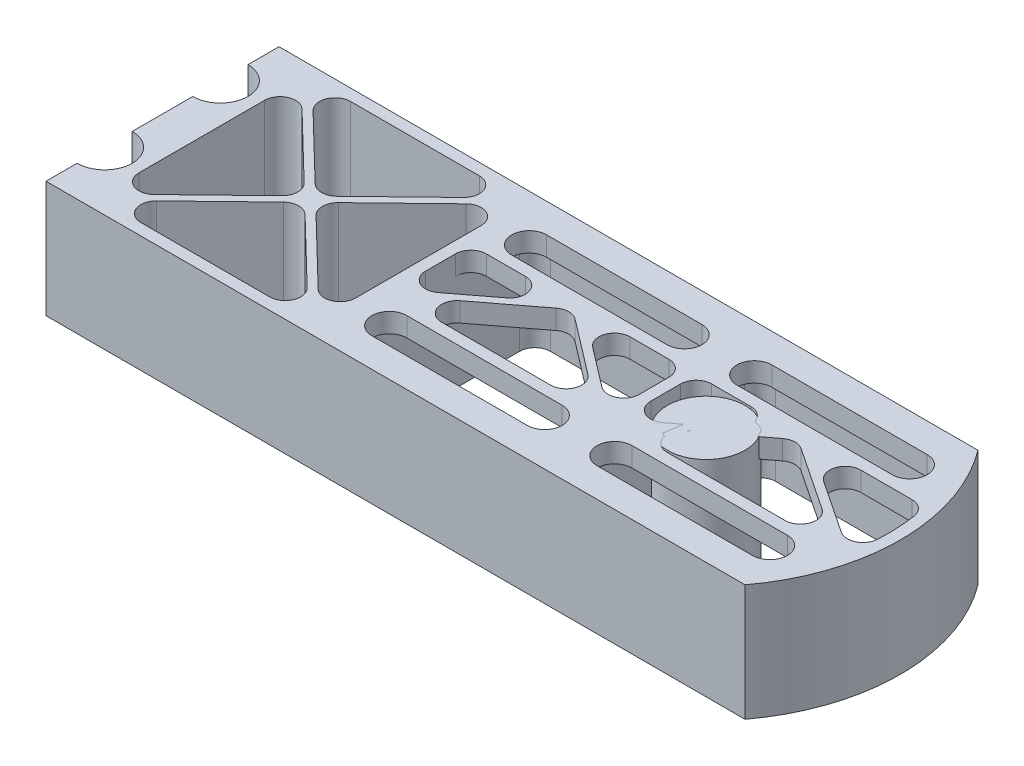
SolidWorks part; units mm, degrees
material "3.1355 (EN-AW 2024)"
ref_plane "Front" through (0, 0, 0) normal (0, 0, 1) x (1, 0, 0)
ref_plane "Top" through (0, 0, 0) normal (0, 1, 0) x (1, 0, 0)
ref_plane "Right" through (0, 0, 0) normal (1, 0, 0) x (0, 0, -1)
sketch "Эскиз1" plane through (0, 0, 0) normal (0, 1, 0) x (1, 0, 0)
  line L0 (0, 0) -> (0, 60) construction
  line L1 (0, 60) -> (180, 60)
  line L2 (190, 60) -> (190, 0) construction
  line L3 (190, 0) -> (180, 0) construction
  line L4 (0, 30) -> (140, 30) construction
  line L5 (0, 60) -> (0, 52)
  line L6 (0, 37.8) -> (0, 22.2)
  line L7 (0, 8) -> (0, 0)
  line L8 (140, 30) -> (190, 30) construction
  line L9 (180, 60) -> (190, 60) construction
  line L10 (180, 0) -> (0, 0)
  circle A0 centre (0, 44.9) radius 7.1 construction
  circle A1 centre (0, 15.1) radius 7.1 construction
  arc A2 (0, 52) -> (0, 37.8) centre (0, 44.9) cw
  arc A3 (0, 8) -> (0, 22.2) centre (0, 15.1) ccw
  arc A4 (180, 0) -> (180, 60) centre (140, 30) ccw
  point P11 (0, 52)
  point P12 (0, 37.8)
  point P20 (180.1659, -0.1217)
  dimension "D2" = 14.2
  dimension "D4" = 29.8
  dimension "D8" = 50
  dimension "D1" = 60
  dimension "D3" = 15.1
  dimension "D5" = 140
  dimension "D6" = 50
  dimension "D7" = 190
extrude "Бобышка-Вытянуть1" add sketch "Эскиз1" along normal blind 30
sketch "Эскиз2" plane through (0, 30, 0) normal (0, 1, 0) x (1, 0, 0)
  line L5 (3, 3) -> (178.4708, 3)
  line L6 (3, 3) -> (178.4708, 3)
  line L12 (3, 5.4558) -> (3, 3)
  line L15 (178.4708, 57) -> (3, 57)
  line L16 (3, 57) -> (3, 54.5442)
  line L17 (3, 35.2558) -> (3, 24.7442)
  line L18 (3, 5.4558) -> (3, 3)
  line L21 (178.4708, 57) -> (3, 57)
  line L22 (3, 57) -> (3, 54.5442)
  line L23 (3, 35.2558) -> (3, 24.7442)
  arc A3 (178.4708, 3) -> (178.4708, 57) centre (140, 30) ccw
  arc A4 (3, 35.2558) -> (3, 54.5442) centre (0, 44.9) ccw
  arc A5 (3, 5.4558) -> (3, 24.7442) centre (0, 15.1) ccw
  arc A6 (3, 35.2558) -> (3, 54.5442) centre (0, 44.9) ccw
  arc A7 (3, 5.4558) -> (3, 24.7442) centre (0, 15.1) ccw
  arc A8 (178.4708, 3) -> (178.4708, 57) centre (140, 30) ccw
  dimension "D1" = 3
extrude "Вырез-Вытянуть1" cut sketch "Эскиз2" against normal through all
sketch "Temp" plane through (0, 30, 0) normal (0, 1, 0) x (1, 0, 0)
  circle A0 centre (140, 30) radius 10
  dimension "D1" = 20
extrude "Бобышка-Вытянуть2" add sketch "Temp" against normal up to surface (30 mm away) separate body up to face at (49.7088, 0, -30)
sketch "Эскиз3" plane through (0, 30, 0) normal (0, 1, 0) x (1, 0, 0)
  line L0 (178.4708, 57) -> (3, 57) construction
  line L1 (174.4166, 48) -> (134.4166, 48) construction
  line L2 (174.4166, 43.5) -> (134.4166, 43.5)
  line L3 (174.4166, 52.5) -> (134.4166, 52.5)
  line L4 (174.4166, 48) -> (183.4166, 48) construction
  line L5 (125.4166, 57) -> (125.4166, 30) construction
  line L6 (0, 30) -> (140, 30) construction
  line L7 (76.4166, 48) -> (116.4166, 48) construction
  line L8 (76.4166, 43.5) -> (116.4166, 43.5)
  line L9 (76.4166, 52.5) -> (116.4166, 52.5)
  line L10 (187, 30) -> (125.4166, 30) construction
  line L11 (76.4166, 12) -> (116.4166, 12) construction
  line L12 (76.4166, 16.5) -> (116.4166, 16.5)
  line L13 (76.4166, 7.5) -> (116.4166, 7.5)
  line L14 (174.4166, 12) -> (134.4166, 12) construction
  line L15 (174.4166, 16.5) -> (134.4166, 16.5)
  line L16 (174.4166, 7.5) -> (134.4166, 7.5)
  line L17 (68.9166, 57) -> (68.9166, 40.5)
  line L18 (68.9166, 40.5) -> (185.8121, 40.5)
  line L19 (178.4708, 57) -> (68.9166, 57)
  line L20 (76.4166, 12) -> (116.4166, 12) construction
  line L21 (76.4166, 16.5) -> (116.4166, 16.5)
  line L22 (76.4166, 7.5) -> (116.4166, 7.5)
  line L23 (174.4166, 12) -> (134.4166, 12) construction
  line L24 (174.4166, 16.5) -> (134.4166, 16.5)
  line L25 (174.4166, 7.5) -> (134.4166, 7.5)
  line L26 (68.9166, 19.5) -> (185.8121, 19.5)
  line L27 (178.4708, 3) -> (68.9166, 3)
  line L28 (68.9166, 3) -> (68.9166, 19.5)
  arc A0 (174.4166, 43.5) -> (174.4166, 52.5) centre (174.4166, 48) ccw
  arc A1 (134.4166, 52.5) -> (134.4166, 43.5) centre (134.4166, 48) ccw
  arc A2 (178.4708, 3) -> (178.4708, 57) centre (140, 30) ccw construction
  arc A3 (76.4166, 43.5) -> (76.4166, 52.5) centre (76.4166, 48) cw
  arc A4 (116.4166, 52.5) -> (116.4166, 43.5) centre (116.4166, 48) cw
  arc A5 (76.4166, 16.5) -> (76.4166, 7.5) centre (76.4166, 12) ccw
  arc A6 (116.4166, 7.5) -> (116.4166, 16.5) centre (116.4166, 12) ccw
  arc A7 (174.4166, 16.5) -> (174.4166, 7.5) centre (174.4166, 12) cw
  arc A8 (134.4166, 7.5) -> (134.4166, 16.5) centre (134.4166, 12) cw
  arc A9 (185.8121, 40.5) -> (178.4708, 57) centre (140, 30) ccw
  arc A10 (76.4166, 16.5) -> (76.4166, 7.5) centre (76.4166, 12) ccw
  arc A11 (116.4166, 7.5) -> (116.4166, 16.5) centre (116.4166, 12) ccw
  arc A12 (174.4166, 16.5) -> (174.4166, 7.5) centre (174.4166, 12) cw
  arc A13 (134.4166, 7.5) -> (134.4166, 16.5) centre (134.4166, 12) cw
  arc A14 (185.8121, 19.5) -> (178.4708, 3) centre (140, 30) cw
  point P1 (154.4166, 48)
  point P20 (96.4166, 48)
  point P28 (96.4166, 12)
  point P35 (154.4166, 12)
  arc M3 (178.4708, 57) -> (178.4708, 3) centre (140, 30) cw
  line M4 (178.4708, 3) -> (3, 3)
  line M10 (3, 57) -> (178.4708, 57)
  dimension "D1" = 4.5
  dimension "D6" = 3
  dimension "D2" = 40
  dimension "D3" = 9
  dimension "D4" = 9
  dimension "D5" = 9
  dimension "D7" = 7.5
extrude "Бобышка-Вытянуть3" add sketch "Эскиз3" against normal blind 5 contours L17 L18 A1 L3 A0 L2 L9 A4 L8 A3 M3 M10 | L28 L26 A6 L13 A5 L12 L16 A8 L15 A7 M4 M3 region at (126.2402, 30, -49.206) region at (126.2402, 30, -10.794)
sketch "Эскиз4" plane through (0, 30, 0) normal (0, 1, 0) x (1, 0, 0)
  line L0 (3, 57) -> (3, 54.5442) construction
  line L1 (3, 35.2558) -> (3, 24.7442) construction
  line L2 (3, 5.4558) -> (3, 3) construction
  line L3 (3, 3) -> (68.9166, 3) construction
  line L4 (68.9166, 57) -> (3, 57) construction
  line L5 (3, 57) -> (3, 54.5442)
  line L6 (3, 35.2558) -> (3, 24.7442)
  line L7 (3, 5.4558) -> (3, 3)
  line L8 (3, 3) -> (10.1, 3)
  line L9 (10.1, 57) -> (3, 57)
  line L10 (10.1, 57) -> (10.1, 3)
  arc A0 (3, 35.2558) -> (3, 54.5442) centre (0, 44.9) ccw construction
  arc A1 (3, 5.4558) -> (3, 24.7442) centre (0, 15.1) ccw construction
  arc A2 (3, 35.2558) -> (3, 54.5442) centre (0, 44.9) ccw
  arc A3 (3, 5.4558) -> (3, 24.7442) centre (0, 15.1) ccw
  line M4 (68.9166, 3) -> (3, 3)
  line M5 (3, 3) -> (3, 5.4558)
  arc M6 (3, 5.4558) -> (3, 24.7442) centre (0, 15.1) ccw
  line M7 (3, 24.7442) -> (3, 35.2558)
  arc M8 (3, 35.2558) -> (3, 54.5442) centre (0, 44.9) ccw
  line M9 (3, 54.5442) -> (3, 57)
  line M10 (3, 57) -> (68.9166, 57)
extrude "Бобышка-Вытянуть4" add sketch "Эскиз4" against normal through all contours L10 M10 M9 M8 | L10 M8 M7 M6 | L10 M6 M5 M4 region at (7.3993, 30, -54.0144) region at (7.3993, 30, -5.9856) region at (7.0952, 30, -30)
sketch "Эскиз6" plane through (0, 30, 0) normal (0, 1, 0) x (1, 0, 0)
  line L0 (65.9166, 57) -> (65.9166, 3)
  line L1 (68.9166, 57) -> (10.1, 57) construction
  line L2 (10.1, 3) -> (68.9166, 3) construction
  line L3 (68.9166, 57) -> (68.9166, 40.5) construction
  line L4 (65.9166, 3) -> (68.9166, 3)
  line L5 (68.9166, 3) -> (68.9166, 57)
  line L6 (68.9166, 57) -> (65.9166, 57)
  dimension "D1" = 3
extrude "Бобышка-Вытянуть5" add sketch "Эскиз6" against normal through all
sketch "Эскиз7" plane through (0, 30, 0) normal (0, 1, 0) x (1, 0, 0)
  line L0 (10.1, 3) -> (65.9166, 57) construction
  line L1 (10.1, 57) -> (65.9166, 3) construction
  line L2 (10.1, 55.6086) -> (36.5701, 30)
  line L3 (11.5382, 3) -> (38.0083, 28.6086)
  line L4 (11.5382, 57) -> (38.0083, 31.3914)
  line L5 (10.1, 4.3914) -> (36.5701, 30)
  line L6 (65.9166, 57) -> (10.1, 57) construction
  line L7 (10.1, 57) -> (10.1, 3) construction
  line L8 (10.1, 3) -> (65.9166, 3) construction
  line L9 (65.9166, 57) -> (65.9166, 3) construction
  line L10 (65.9166, 57) -> (64.4784, 57)
  line L11 (10.1, 57) -> (10.1, 55.6086)
  line L12 (10.1, 3) -> (11.5382, 3)
  line L13 (65.9166, 57) -> (65.9166, 55.6086)
  line L14 (11.5382, 57) -> (10.1, 57)
  line L15 (10.7953, 57.7187) -> (66.6119, 3.7187) construction
  line L16 (9.4047, 56.2813) -> (65.2213, 2.2813) construction
  line L17 (65.9166, 4.3914) -> (65.9166, 3)
  line L18 (9.4047, 3.7187) -> (65.2213, 57.7187) construction
  line L19 (10.7953, 2.2813) -> (66.6119, 56.2813) construction
  line L20 (64.4784, 3) -> (65.9166, 3)
  line L21 (10.1, 4.3914) -> (10.1, 3)
  line L22 (39.4465, 30) -> (65.9166, 55.6086)
  line L23 (39.4465, 30) -> (65.9166, 4.3914)
  line L24 (38.0083, 31.3914) -> (64.4784, 57)
  line L25 (38.0083, 28.6086) -> (64.4784, 3)
  dimension "D1" = 1
  dimension "D2" = 1
extrude "Бобышка-Вытянуть6" add sketch "Эскиз7" against normal through all
sketch "Эскиз9" plane through (0, 25, 0) normal (0, -1, 0) x (1, 0, 0)
  line L0 (120.9166, -12) -> (129.9166, -12) construction
  line L1 (125.4166, -3) -> (125.4166, -57) construction
  line L2 (68.9166, -57) -> (178.4708, -57) construction
  line L3 (123.9166, -3) -> (123.9166, -57)
  line L4 (101.5292, -3) -> (68.9166, -3) construction
  line L5 (126.9166, -3) -> (126.9166, -57)
  line L6 (123.9166, -3) -> (126.9166, -3)
  line L7 (123.9166, -57) -> (126.9166, -57)
  arc A0 (116.4166, -16.5) -> (116.4166, -7.5) centre (116.4166, -12) ccw construction
  arc A1 (134.4166, -16.5) -> (134.4166, -7.5) centre (134.4166, -12) ccw construction
  point P8 (125.4166, -12)
  dimension "D1" = 1.5
  dimension "D2" = 1.5
extrude "Бобышка-Вытянуть8" add sketch "Эскиз9" along normal through all and the other way through all
sketch "Эскиз8" plane through (0, 30, 0) normal (0, 1, 0) x (1, 0, 0)
  line L0 (96.4166, 43.5) -> (96.4166, 16.5) construction
  line L1 (76.4166, 43.5) -> (116.4166, 43.5) construction
  line L2 (76.4166, 16.5) -> (116.4166, 16.5) construction
  line L3 (154.4166, 43.5) -> (154.4166, 16.5) construction
  line L4 (174.4166, 43.5) -> (134.4166, 43.5) construction
  line L5 (174.4166, 16.5) -> (134.4166, 16.5) construction
  line L6 (68.9166, 19.5) -> (96.4166, 40.5) construction
  line L7 (116.4166, 48) -> (134.4166, 48) construction
  line L8 (125.4166, 48) -> (125.4166, 19.5) construction
  line L9 (68.9166, 40.5) -> (123.9166, 40.5) construction
  line L10 (96.4166, 40.5) -> (123.9166, 19.5) construction
  line L11 (126.9166, 19.5) -> (154.4401, 40.4052) construction
  line L12 (154.4401, 40.4052) -> (185.8121, 19.5) construction
  line L13 (70.5643, 19.5) -> (96.4166, 39.2418)
  line L14 (96.4166, 39.2418) -> (122.2689, 19.5)
  line L15 (128.5699, 19.5) -> (154.478, 39.1782)
  line L16 (154.478, 39.1782) -> (184.0088, 19.5)
  line L17 (68.9166, 20.7582) -> (94.7689, 40.5)
  line L18 (98.0643, 40.5) -> (123.9166, 20.7582)
  line L19 (126.9166, 20.7557) -> (152.9116, 40.5)
  line L20 (122.2689, 19.5) -> (123.9166, 19.5)
  line L22 (94.7689, 40.5) -> (98.0643, 40.5)
  line L23 (68.9166, 19.5) -> (68.9166, 40.5) construction
  line L24 (68.9166, 19.5) -> (123.9166, 19.5) construction
  line L25 (123.9166, 19.5) -> (123.9166, 40.5) construction
  line L26 (126.9166, 40.5) -> (126.9166, 19.5) construction
  line L27 (126.9166, 40.5) -> (185.8121, 40.5) construction
  line L28 (126.9166, 19.5) -> (185.8121, 19.5) construction
  line L29 (68.9166, 19.5) -> (68.9166, 20.7582)
  line L30 (68.9166, 19.5) -> (70.5643, 19.5)
  line L31 (123.9166, 19.5) -> (123.9166, 20.7582)
  line L32 (126.9166, 20.7557) -> (126.9166, 19.5)
  line L33 (152.9116, 40.5) -> (156.1011, 40.5)
  line L34 (126.9166, 19.5) -> (128.5699, 19.5)
  line L35 (184.0088, 19.5) -> (185.8121, 19.5)
  line L36 (154.4021, 41.6321) -> (186.3666, 20.3322) construction
  line L37 (154.478, 39.1782) -> (185.2576, 18.6678) construction
  line L38 (156.1011, 40.5) -> (186.0401, 20.5497)
  line L39 (127.5214, 18.7037) -> (154.478, 39.1782) construction
  line L40 (126.3117, 20.2963) -> (154.4021, 41.6321) construction
  line L42 (96.4166, 41.7582) -> (124.5235, 20.2948) construction
  line L43 (68.3097, 20.2948) -> (96.4166, 41.7582) construction
  line L44 (69.5235, 18.7052) -> (96.4166, 39.2418) construction
  line L45 (96.4166, 39.2418) -> (123.3097, 18.7052) construction
  arc A1 (185.8121, 19.5) -> (185.8121, 40.5) centre (140, 30) ccw construction
  arc A2 (185.8121, 19.5) -> (186.0401, 20.5497) centre (140, 30) ccw
  point P26 (69.5235, 18.7052)
  point P27 (96.4324, 39.2539)
  point P28 (125.4324, 18.2539)
  point P30 (185.2357, 18.6828)
  point P31 (68.3097, 20.2948)
  point P32 (96.4007, 41.7461)
  point P33 (125.4007, 20.7461)
  point P34 (154.3931, 42.8858)
  point P35 (186.3885, 20.3172)
  point P49 (154.4166, 40.5)
  dimension "D1" = 1
  dimension "D2" = 1
extrude "Бобышка-Вытянуть7" add sketch "Эскиз8" against normal up to surface (5 mm away) up to face at (96.4166, 25, -12)
fillet "Скругление1" radius 4 12 edges at (11.5382, 15, -57) (38.0083, 15, -31.3914) (64.4784, 15, -57) (65.9166, 15, -55.6086) (39.4465, 15, -30) (65.9166, 15, -4.3914) (11.5382, 15, -3) (64.4784, 15, -3) (38.0083, 15, -28.6086) (10.1, 15, -4.3914) (36.5701, 15, -30) (10.1, 15, -55.6086)
fillet "Скругление2" radius 4 8 edges at (178.4708, 12.5, -57) (178.4708, 12.5, -3) (126.9166, 12.5, -3) (126.9166, 12.5, -57) (123.9166, 12.5, -3) (68.9166, 12.5, -3) (68.9166, 12.5, -57) (123.9166, 12.5, -57)
fillet "Скругление3" radius 4 18 edges at (98.0643, 27.5, -40.5) (123.9166, 27.5, -40.5) (123.9166, 27.5, -20.7582) (122.2689, 27.5, -19.5) (96.4166, 27.5, -39.2418) (70.5643, 27.5, -19.5) (94.7689, 27.5, -40.5) (68.9166, 27.5, -40.5) (68.9166, 27.5, -20.7582) (185.8121, 27.5, -40.5) (156.1011, 27.5, -40.5) (186.0401, 27.5, -20.5497) (184.0088, 27.5, -19.5) (154.478, 27.5, -39.1782) (128.5699, 27.5, -19.5) (126.9166, 27.5, -20.7557) (152.9116, 27.5, -40.5) (126.9166, 27.5, -40.5)
equation "\"D3@Эскиз1\"=8+\"D2@Эскиз1\"/2"
equation "\"D7@Эскиз3\"=\"D1@Эскиз3\"+3"
